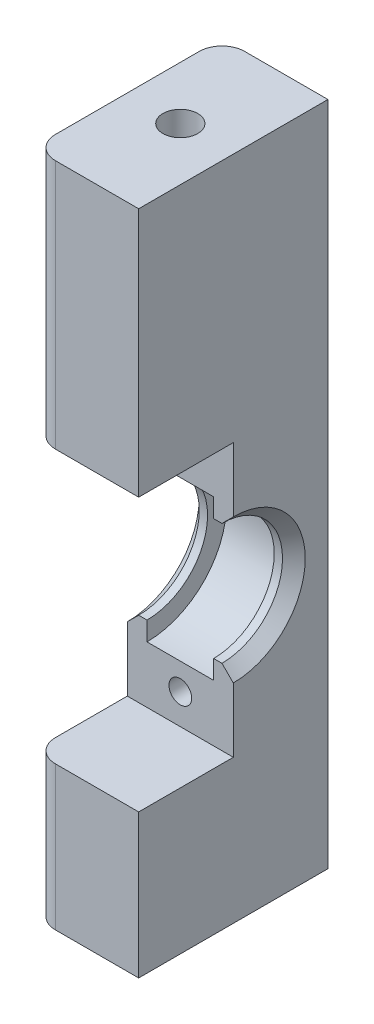
SolidWorks part; units mm, degrees
ref_plane "Спереди" through (0, 0, 0) normal (0, 0, 1) x (1, 0, 0)
ref_plane "Сверху" through (0, 0, 0) normal (0, 1, 0) x (1, 0, 0)
ref_plane "Справа" through (0, 0, 0) normal (1, 0, 0) x (0, 0, -1)
sketch "Эскиз1" plane through (0, 0, 0) normal (0, 0, 1) x (1, 0, 0)
  line L1 (-3.5, -22) -> (3.5, -22)
  line L2 (-3.5, -22) -> (-3.5, 22)
  line L3 (-3.5, 22) -> (3.5, 22)
  line L4 (3.5, -22) -> (3.5, 22)
  line L5 (-3.5, -22) -> (3.5, 22) construction
  line L6 (-3.5, 22) -> (3.5, -22) construction
  point P0 (0, 0)
  dimension "D1" = 7
  dimension "D2" = 44
extrude "тело" add sketch "Эскиз1" along normal blind 12.5
sketch "Эскиз6" plane through (-3.5, 0, 0) normal (-1, 0, 0) x (0, 0, 1)
  line L1 (12.5, 22) -> (12.5, -22) construction
  circle A0 centre (6.25, -3.5) radius 4
  dimension "D1" = 8
  dimension "D2" = 6.25
sketch "Эскиз7" plane through (-3.5, 0, 0) normal (-1, 0, 0) x (0, 0, 1)
  line L0 (12.5, 22) -> (12.5, -22) construction
  line L1 (6.25, 5.5) -> (12.5, 5.5)
  line L2 (6.25, 5.5) -> (6.25, -12.5)
  line L3 (6.25, -12.5) -> (12.5, -12.5)
  line L4 (12.5, 5.5) -> (12.5, -12.5)
  line L6 (12.5, -22) -> (0, -22) construction
  point P6 (6.25, -3.5)
  point P7 (6.25, -3.5)
  dimension "D1" = 18
  dimension "D2" = 6.25
  dimension "D3" = 18.5
sketch "Эскиз11" plane through (0, -22, 0) normal (0, -1, 0) x (1, 0, 0)
  line L0 (-3.5, 12.5) -> (-3.5, 0) construction
  line L2 (-3.5, 12.5) -> (3.5, 12.5) construction
  circle A0 centre (0, 6.25) radius 1.15
  point P6 (-3.5, 6.25)
  point P10 (0, 12.5)
  dimension "D1" = 2.3
fillet "Скругление3" radius 1.5 2 edges at (-3.5, 0, 12.5) (-3.5, 0, 0)
extrude "Вырез под ось подшипника" cut sketch "Эскиз6" against normal up to next
extrude "Вырез под крепление подшипника" cut sketch "Эскиз7" against normal up to next
extrude "Крепежное отверстие снизу" cut sketch "Эскиз11" against normal blind 8
mirror "Крепежное отверстиее сверху" about plane through (0, 0, 0) normal (0, 1, 0) of "Крепежное отверстие снизу"
ref_plane "Средняя продольная плоскость" through (0, 0, 0) normal (1, 0, 0) x (0, 0, -1)
sketch "Эскиз12" plane through (0, 0, 0) normal (1, 0, 0) x (0, 0, -1)
  circle A0 centre (-6.25, -3.5) radius 5.25
  dimension "D1" = 10.5
extrude "Вырез под подшипник" cut sketch "Эскиз12" against normal blind 2.2 and the other way blind 2.2
sketch "Эскиз13" plane through (0, 0, 6.25) normal (0, 0, 1) x (1, 0, 0)
  line L1 (0, -10.5) -> (0, 3.5) construction
  line L6 (2.2, 1.75) -> (-2.2, 1.75) construction
  line L7 (3.5, 5.5) -> (-3.5, 5.5) construction
  circle A0 centre (0, 3.5) radius 0.75
  circle A1 centre (0, -10.5) radius 0.75
  point P20 (0, 5.5)
  dimension "D2" = 1.5
  dimension "D3" = 1.75
  dimension "D1" = 14
extrude "Крепежные отверстия" cut sketch "Эскиз13" against normal blind 5.5
chamfer "Фаска1" distance 0.75 angle 45 2 edges at (3.5, -3.5, 2.25) (-3.5, -3.5, 2.25)
